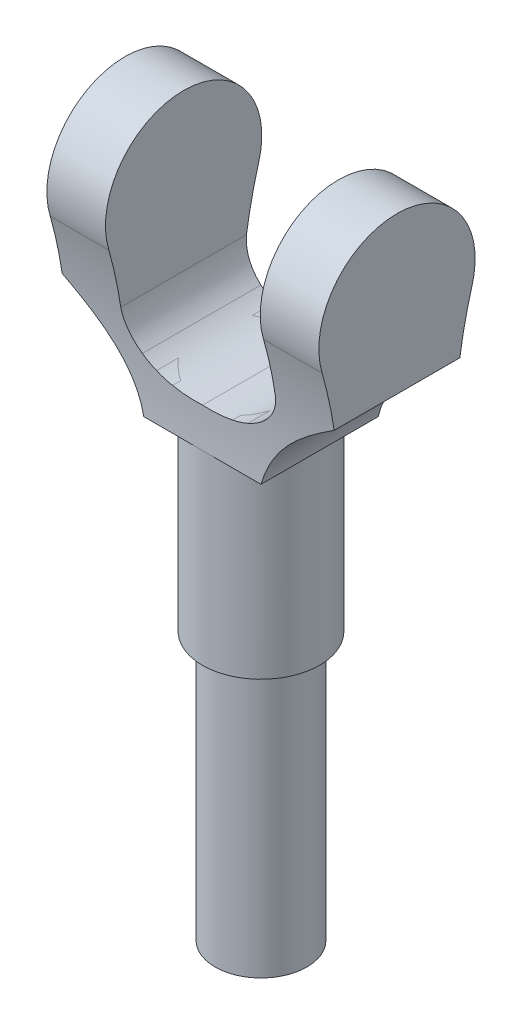
SolidWorks part; units mm, degrees
ref_plane "Front Plane" through (0, 0, 0) normal (0, 0, 1) x (1, 0, 0)
ref_plane "Top Plane" through (0, 0, 0) normal (0, 1, 0) x (1, 0, 0)
ref_plane "Right Plane" through (0, 0, 0) normal (1, 0, 0) x (0, 0, -1)
sketch "Sketch1" plane through (0, 0, 0) normal (0, 1, 0) x (1, 0, 0)
  circle A0 centre (0, 0) radius 11.75
  dimension "D1" = 23.5
extrude "Boss-Extrude1" add sketch "Sketch1" along normal blind 68.5
sketch "Sketch2" plane through (0, 68.5, 0) normal (0, 1, 0) x (1, 0, 0)
  circle A0 centre (0, 0) radius 15
extrude "Boss-Extrude2" add sketch "Sketch2" along normal blind 90
sketch "Sketch3" plane through (0, 0, 0) normal (0, 0, 1) x (1, 0, 0)
  line L0 (0, 203.8403) -> (0, 112.2786) construction
  line L1 (-42.3089, 138.5) -> (60.9499, 138.5) construction
  line L2 (-42.3089, 178.5) -> (66.2942, 178.5) construction
  line L4 (-15, 158.5) -> (-15, 68.5) construction
  line L5 (15, 68.5) -> (15, 158.5) construction
  line L6 (19.8, 178.5) -> (34.8, 178.5)
  line L7 (15, 178.5) -> (35, 178.5)
  line L8 (19.8, 138.5) -> (19.8, 178.5)
  line L9 (-19.8, 138.5) -> (-19.8, 178.5)
  line L10 (-19.8, 178.5) -> (-34.8, 178.5)
  line L11 (-15, 116.1097) -> (15, 116.1097)
  line L12 (-34.8, 138.5) -> (-34.8, 178.5)
  line L13 (-2.0813, 126.3958) -> (2.0813, 126.3958)
  line L14 (34.8, 138.5) -> (34.8, 178.5)
  spline S0 degree 3 poles (-19.8, 138.5) (-19.342, 130.1136) (-9.499, 125.4962) (-2.0813, 126.3958) knots 0 0 0 0 1 1 1 1
  spline S1 degree 3 poles (-34.8, 138.5) (-26.5938, 132.957) (-17.535, 126.3267) (-15, 116.1097) knots 0 0 0 0 1 1 1 1
  spline S2 degree 3 poles (19.8, 138.5) (19.342, 130.1136) (9.499, 125.4962) (2.0813, 126.3958) knots 0 0 0 0 1 1 1 1
  spline S3 degree 3 poles (34.8, 138.5) (26.5938, 132.957) (17.535, 126.3267) (15, 116.1097) knots 0 0 0 0 1 1 1 1
  point P9 (-15, 138.5)
  point P10 (15, 138.5)
  dimension "D1" = 15
  dimension "D2" = 40
  dimension "D3" = 19.8
extrude "Boss-Extrude8" add sketch "Sketch3" along normal blind 20 and the other way blind 20 contours S3 L14 L6 L8 S2 L13 S0 L9 L10 L12 S1 L11 region at (27.3, 177.5653, 0)
sketch "Sketch4" plane through (0, 0, 0) normal (1, 0, 0) x (0, 0, -1)
  line L0 (-41.2208, 158.5) -> (58.3363, 158.5) construction
  line L1 (0, 184.7476) -> (0, 121.27) construction
  line L2 (20, 178.5) -> (-20, 178.5) construction
  line L3 (-20, 116.1097) -> (-15, 116.1097)
  line L4 (20, 116.1097) -> (15, 116.1097)
  line L5 (20, 116.1097) -> (20, 158.5)
  line L6 (-20, 116.1097) -> (-20, 158.5)
  line L8 (-20, 178.5) -> (20, 178.5)
  line L9 (-20, 178.5) -> (-20, 158.5)
  line L11 (20, 178.5) -> (20, 158.5)
  circle A0 centre (0, 158.5) radius 20
  spline S0 degree 2 poles (19.3186, 153.324) (14.0693, 135.1723) (15, 116.1097) knots 0 0 0 1 1 1
  spline S1 degree 2 poles (-19.3186, 153.324) (-14.0693, 135.1723) (-15, 116.1097) knots 0 0 0 1 1 1
  dimension "D1" = 20
extrude "Cut-Extrude1" cut sketch "Sketch4" against normal through all both and the other way through all contours S1 A0 L6 L3 | A0 L8 L9 | A0 L11 L8 | A0 S0 L4 L5 region at (0, 131.4834, 17.8463) region at (0, 174.0326, 15.5326) region at (0, 174.0326, -15.5326) region at (0, 131.4834, -17.8463)
sketch "Sketch5" plane through (0, 0, 0) normal (0, 0, 1) x (1, 0, 0)
  line L0 (-15, 158.5) -> (-15.1952, 130.1076)
  line L1 (0, 158.5) -> (0, 146.3461) construction
  line L2 (15, 158.5) -> (15.1952, 130.1076)
  line L3 (15, 158.5) -> (-15, 158.5)
  spline S0 degree 3 poles (-15.1952, 130.1076) (-10.9653, 126.7392) (-5.2549, 125.8386) (0, 126.1282) knots 0 0 0 0 1 1 1 1
  spline S1 degree 3 poles (-2.0813, 126.3958) (-9.499, 125.4962) (-19.342, 130.1136) (-19.8, 138.5) knots 0 0 0 0 1 1 1 1 construction
  spline S2 degree 3 poles (15.1952, 130.1076) (10.9653, 126.7392) (5.2549, 125.8386) (0, 126.1282) knots 0 0 0 0 1 1 1 1
  point P15 (-15.1952, 130.1076)
  point P16 (-15, 158.5)
  point P17 (-15, 158.5)
extrude "Cut-Extrude3" cut sketch "Sketch5" against normal through all both and the other way through all
